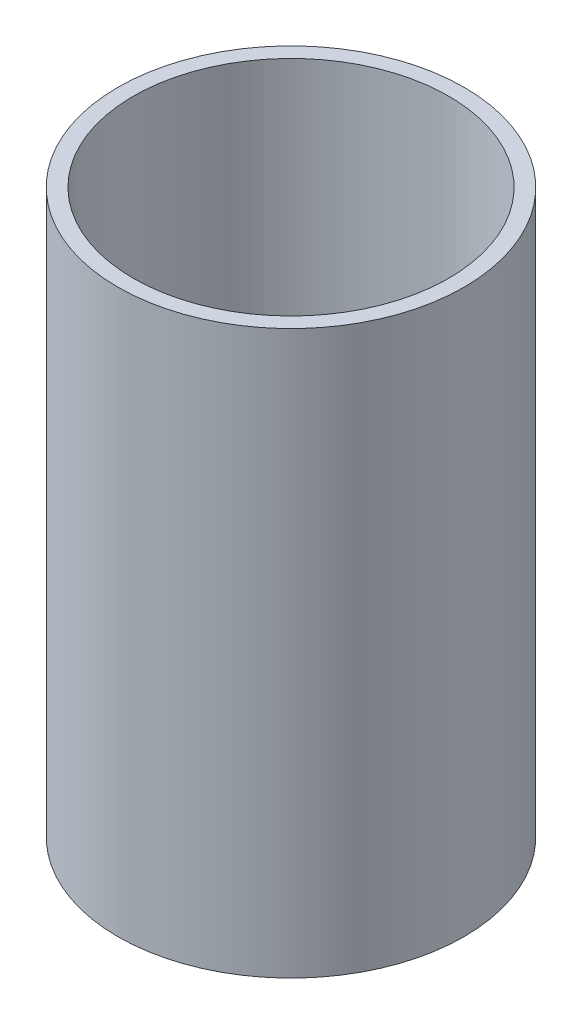
SolidWorks part; units mm, degrees
ref_plane "Front Plane" through (0, 0, 0) normal (0, 0, 1) x (1, 0, 0)
ref_plane "Top Plane" through (0, 0, 0) normal (0, 1, 0) x (1, 0, 0)
ref_plane "Right Plane" through (0, 0, 0) normal (1, 0, 0) x (0, 0, -1)
sketch "Sketch1" plane through (0, 0, 0) normal (0, 1, 0) x (1, 0, 0)
  circle A0 centre (0, 0) radius 52.5
  dimension "SLEEVE_OD" = 105
extrude "Boss-Extrude1" add sketch "Sketch1" along normal blind 170.5934
sketch "Sketch2" plane through (0, 0, 0) normal (0, 1, 0) x (1, 0, 0)
  circle A0 centre (0, 0) radius 47.8389
  dimension "BORE_D" = 95.6778
extrude "Cut-Extrude1" cut sketch "Sketch2" along normal through all
chamfer "Chamfer1" distance 2.0984 angle 69.523 rebuild error yes
